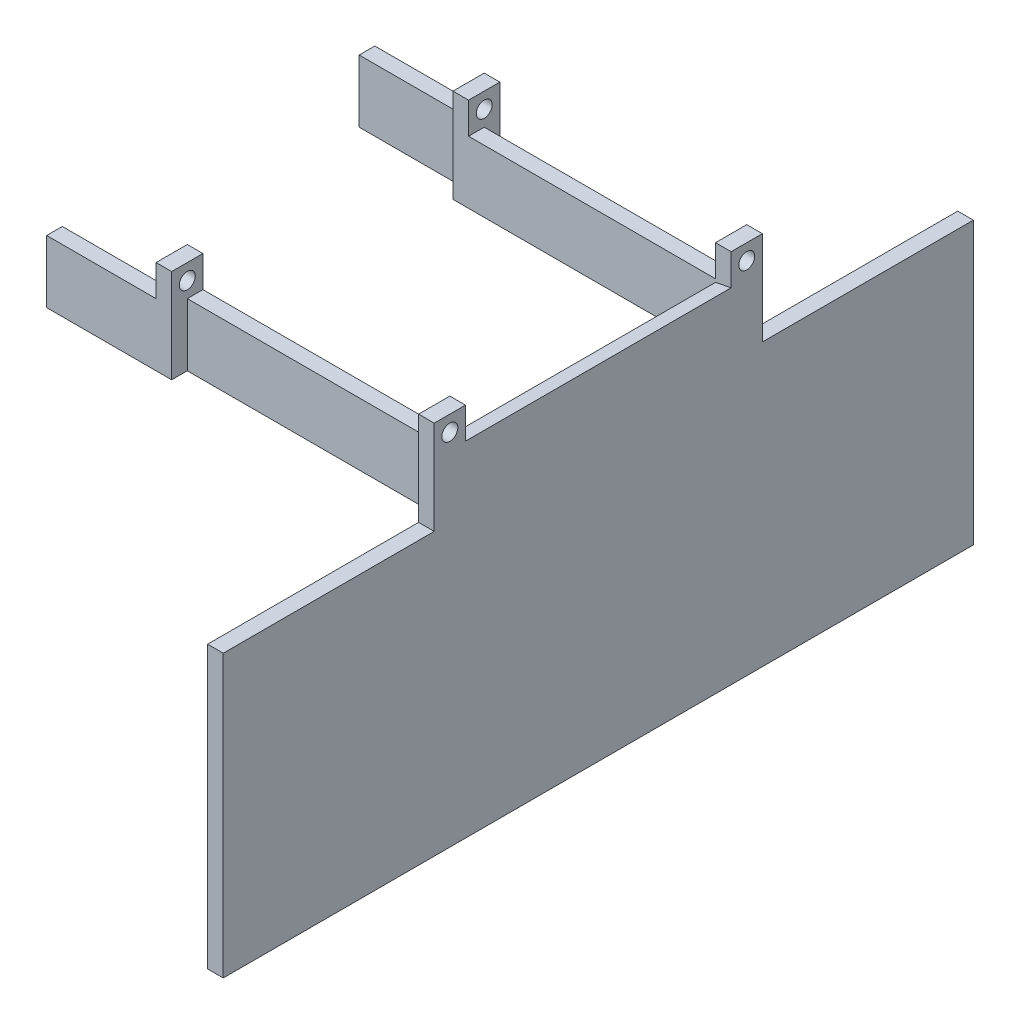
SolidWorks part; units mm, degrees
ref_plane "Front Plane" through (0, 0, 0) normal (0, 0, 1) x (1, 0, 0)
ref_plane "Top Plane" through (0, 0, 0) normal (0, 1, 0) x (1, 0, 0)
ref_plane "Right Plane" through (0, 0, 0) normal (1, 0, 0) x (0, 0, -1)
sketch "Sketch1" plane through (0, 0, 0) normal (0, 1, 0) x (1, 0, 0)
  line L0 (3.175, 114.3) -> (0, 114.3)
  line L1 (0, 0) -> (113.03, 0)
  line L2 (0, 0) -> (0, 6.35)
  line L3 (0, 120.65) -> (113.03, 120.65)
  line L4 (113.03, 0) -> (113.03, 120.65)
  line L5 (3.175, 114.3) -> (106.68, 114.3)
  line L7 (3.175, 6.35) -> (106.68, 6.35)
  line L8 (106.68, 114.3) -> (106.68, 6.35)
  line L9 (3.175, 6.35) -> (0, 6.35)
  line L10 (0, 114.3) -> (0, 120.65)
  dimension "D1" = 120.65
  dimension "D2" = 106.68
  dimension "D3" = 6.35
  dimension "D5" = 6.35
  dimension "D6" = 107.95
extrude "Boss-Extrude1" add sketch "Sketch1" along normal blind 25.4
sketch "Sketch2" plane through (0, 0, 0) normal (0, 0, 1) x (1, 0, 0)
  line L0 (113.03, 25.4) -> (106.68, 24.13)
  line L1 (106.68, 24.13) -> (106.68, 25.4)
  line L2 (0, 25.4) -> (113.03, 25.4) construction
  line L4 (106.68, 25.4) -> (113.03, 25.4)
  dimension "D2" = 1.27
extrude "Cut-Extrude1" cut sketch "Sketch2" against normal up to surface (114.3 mm away) from surface up to face at (53.34, 12.7, -114.3) starting at face at (53.34, 12.7, -6.35)
sketch "Sketch3" plane through (0, 0, 0) normal (0, 0, 1) x (1, 0, 0)
  line L0 (0, 25.4) -> (113.03, 25.4) construction
  line L1 (6.35, 25.4) -> (-44.45, 25.4)
  line L2 (6.35, 25.4) -> (6.35, 0)
  line L3 (6.35, 0) -> (-44.45, 0)
  line L4 (-44.45, 25.4) -> (-44.45, 0)
  line L5 (0, 25.4) -> (0, 0) construction
  dimension "D1" = 6.35
  dimension "D2" = 44.45
extrude "Boss-Extrude2" add sketch "Sketch3" along normal blind 6.35
extrude "Boss-Extrude3" add sketch "Sketch3<2>" against normal blind 6.35 from surface starting at face at (56.515, 12.7, -120.65)
sketch "Sketch3<2>" plane through (0, 0, 0) normal (0, 0, 1) x (1, 0, 0) same geometry as "Sketch3"
sketch "Sketch4" plane through (0, 0, 0) normal (0, -1, 0) x (1, 0, 0)
  line L1 (113.03, 92.075) -> (106.68, 92.075)
  line L2 (113.03, 92.075) -> (113.03, -212.725)
  line L3 (113.03, -212.725) -> (106.68, -212.725)
  line L4 (106.68, 92.075) -> (106.68, -212.725)
  line L6 (113.03, 0) -> (113.03, -120.65) construction
  line L7 (106.68, -114.3) -> (106.68, -6.35) construction
  point P10 (106.68, -60.325)
  point P11 (106.68, -60.325)
  dimension "D1" = 304.8
extrude "Boss-Extrude4" add sketch "Sketch4" along normal blind 114.3
sketch "Sketch8" plane through (0, 25.4, 0) normal (0, 1, 0) x (1, 0, 0)
  line L0 (113.03, 60.325) -> (-5.0576, 60.325) construction
  line L1 (113.03, -6.35) -> (106.68, -6.35)
  line L2 (113.03, -6.35) -> (113.03, 6.35)
  line L3 (113.03, 6.35) -> (106.68, 6.35)
  line L4 (106.68, -6.35) -> (106.68, 6.35)
  line L6 (56.515, 114.3) -> (56.515, -20.9935) construction
  line L7 (0, 114.3) -> (113.03, 114.3) construction
  line L8 (113.03, 114.3) -> (113.03, 6.35) construction
  line L9 (6.35, -6.35) -> (6.35, 6.35)
  line L10 (0, 6.35) -> (6.35, 6.35)
  line L11 (0, -6.35) -> (0, 6.35)
  line L12 (0, -6.35) -> (6.35, -6.35)
  line L22 (0, 127) -> (6.35, 127)
  line L23 (0, 127) -> (0, 114.3)
  line L24 (0, 114.3) -> (6.35, 114.3)
  line L25 (6.35, 127) -> (6.35, 114.3)
  line L26 (106.68, 127) -> (106.68, 114.3)
  line L27 (113.03, 114.3) -> (106.68, 114.3)
  line L28 (113.03, 127) -> (113.03, 114.3)
  line L29 (113.03, 127) -> (106.68, 127)
  dimension "D1" = 12.7
extrude "Boss-Extrude7" add sketch "Sketch8" against normal up to surface (25.4 mm away) from offset 12.7 up to face at (109.855, 0, 46.0375)
sketch "Sketch9" plane through (6.35, 0, 0) normal (1, 0, 0) x (0, 0, -1)
  line L1 (-6.35, 38.1) -> (6.35, 38.1) construction
  line L2 (-6.35, 38.1) -> (-6.35, 0) construction
  line L3 (60.325, 36.7762) -> (60.325, 19.9574) construction
  line L4 (6.35, 38.1) -> (6.35, 0) construction
  circle A0 centre (0, 31.75) radius 3.2385
  circle A1 centre (120.65, 31.75) radius 3.2385
  dimension "D1" = 6.477
  dimension "D3" = 6.35
  dimension "D4" = 53.975
  dimension "D2" = 6.35
extrude "Cut-Extrude2" cut sketch "Sketch9" against normal through all both and the other way through all
equation "\"tightTol\" = 0.005in"
equation "\"normTol\"= 0.01in"
equation "\"looseTol\"= 0.02in"
equation "\"D1@Sketch9\"=\"tightTol\"+0.250000in"
